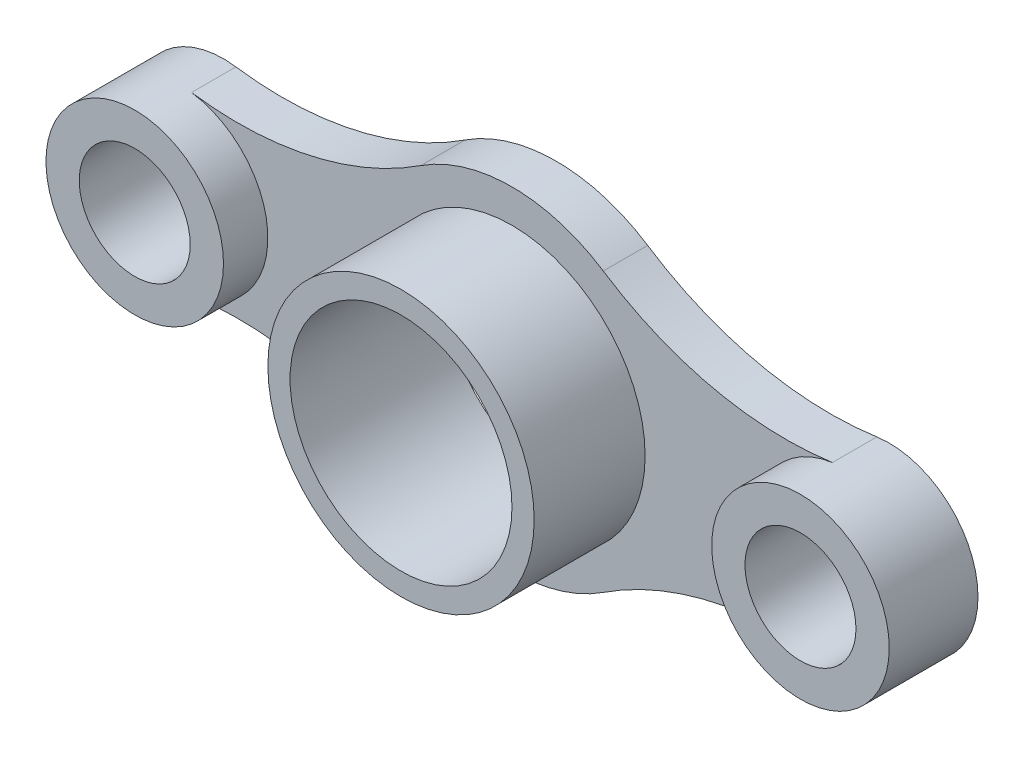
SolidWorks part; units mm, degrees
ref_plane "Front Plane" through (0, 0, 0) normal (0, 0, 1) x (1, 0, 0)
ref_plane "Top Plane" through (0, 0, 0) normal (0, 1, 0) x (1, 0, 0)
ref_plane "Right Plane" through (0, 0, 0) normal (1, 0, 0) x (0, 0, -1)
sketch "Sketch1" plane through (0, 0, 0) normal (0, 0, 1) x (1, 0, 0)
  line L0 (0, 127.6669) -> (0, -127.6669) construction
  line L1 (-210.8432, 0) -> (210.8432, 0) construction
  line L2 (-150, 45.9135) -> (-150, -45.9135) construction
  circle A0 centre (0, 0) radius 50
  circle A1 centre (0, 0) radius 60
  arc A2 (-41.1389, -62.7104) -> (41.1389, -62.7104) centre (0, 0) ccw
  arc A3 (-144.4035, 39.6066) -> (-150, 40) centre (-150, 0) ccw
  circle A4 centre (-150, 0) radius 25
  arc A5 (-144.4035, 39.6066) -> (-41.1389, 62.7104) centre (-123.4167, 188.1311) ccw
  arc A6 (-144.4035, -39.6066) -> (-41.1389, -62.7104) centre (-123.4167, -188.1311) cw
  circle A7 centre (150, 0) radius 25
  arc A9 (144.4035, -39.6066) -> (41.1389, -62.7104) centre (123.4167, -188.1311) ccw
  arc A10 (144.4035, 39.6066) -> (41.1389, 62.7104) centre (123.4167, 188.1311) cw
  arc A11 (41.1389, 62.7104) -> (-41.1389, 62.7104) centre (0, 0) ccw
  arc A12 (-150, -40) -> (-144.4035, -39.6066) centre (-150, 0) ccw
  circle A13 centre (-150, 0) radius 40
  circle A14 centre (150, 0) radius 40
  point P4 (0, 0)
  point P8 (0, 0)
  point P14 (-150, 0)
  dimension "D1" = 100
  dimension "D2" = 120
  dimension "D3" = 150
  dimension "D5" = 50
  dimension "D7" = 150
  dimension "D8" = 80
  dimension "D4" = 150
extrude "Boss-Extrude1" add sketch "Sketch1" along normal blind 20 contours A10 A11 A5 A3 A6 A2 A9 A7 A4 A1 region at (-89.9557, -38.5742, 0)
extrude "Boss-Extrude2" add sketch "Sketch1<3>" along normal blind 70 contours A1 A0 region at (-58.3029, 0, 0)
sketch "Sketch1<3>" plane through (0, 0, 0) normal (0, 0, 1) x (1, 0, 0) same geometry as "Sketch1"
extrude "Boss-Extrude3" add sketch "Sketch1<5>" along normal blind 40 contours A3 A13 A12 A4 | A14 A7 region at (-147.2742, -38.7729, 0) region at (111.1314, 0, 0)
sketch "Sketch1<5>" plane through (0, 0, 0) normal (0, 0, 1) x (1, 0, 0) same geometry as "Sketch1"
